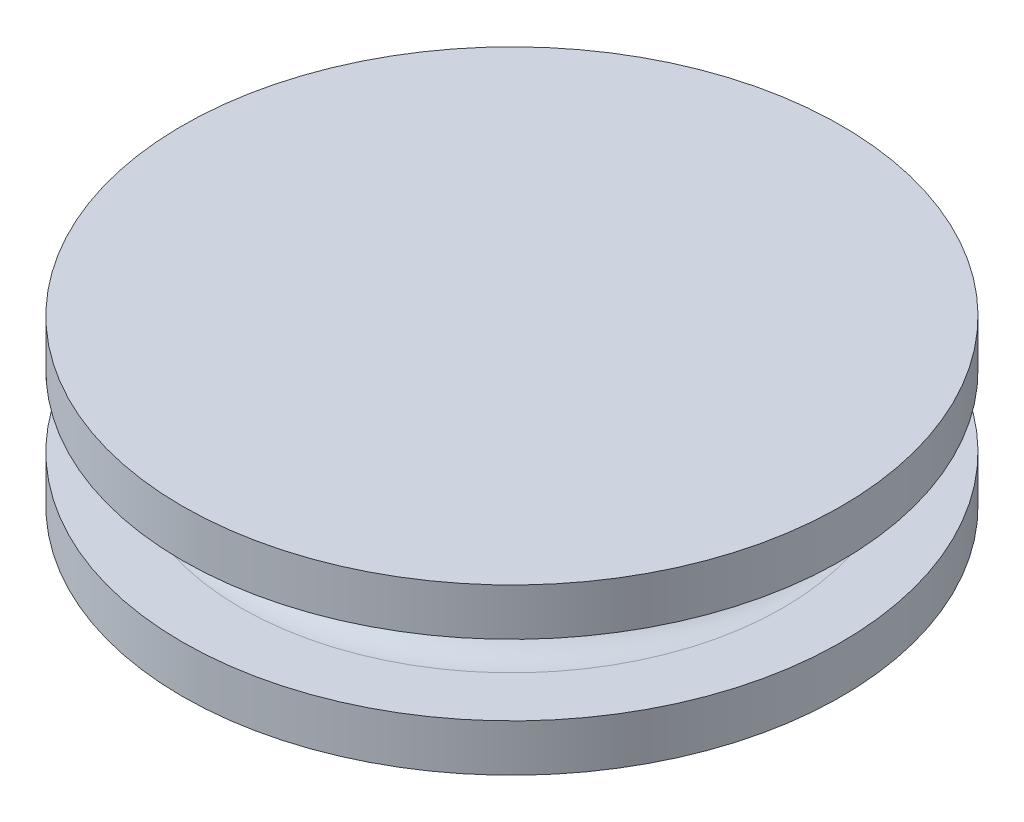
SolidWorks part; units mm, degrees
material "ABS"
ref_plane "正面" through (0, 0, 0) normal (0, 0, 1) x (1, 0, 0)
ref_plane "平面" through (0, 0, 0) normal (0, 1, 0) x (1, 0, 0)
ref_plane "右側面" through (0, 0, 0) normal (1, 0, 0) x (0, 0, -1)
sketch "ｽｹｯﾁ1" plane through (0, 0, 0) normal (0, 0, 1) x (1, 0, 0)
  line L0 (0, 0) -> (0, 6) construction
  line L1 (0, 3.5) -> (-14, 3.5)
  line L2 (-14, 3.5) -> (-14, 1.5)
  line L3 (-14, 1.5) -> (-11.5, 1.5)
  line L4 (-10, 0) -> (0, 0) construction
  line L5 (-14, -3.5) -> (-14, -1.5)
  line L6 (-14, -1.5) -> (-11.5, -1.5)
  line L7 (0, -3.5) -> (-14, -3.5)
  line L8 (0, 3.5) -> (0, -3.5)
  arc A0 (-11.5, 1.5) -> (-11.5, -1.5) centre (-11.5, 0) cw
  dimension "D1" = 3.5
  dimension "D2" = 1.5
  dimension "D3" = 10
  dimension "D4" = 2.5
revolve "回転1" add sketch "ｽｹｯﾁ1" angle 360 about L8
